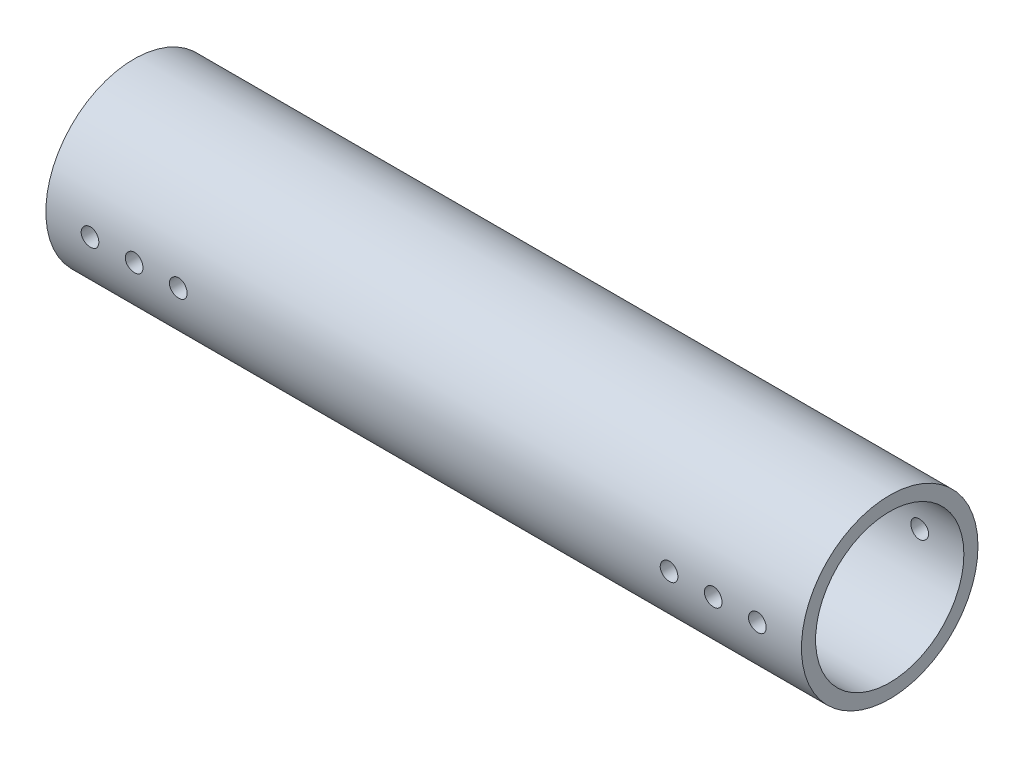
SolidWorks part; units mm, degrees
material "Zoltek Panex 33"
ref_plane "Спереди" through (0, 0, 0) normal (0, 0, 1) x (1, 0, 0)
ref_plane "Сверху" through (0, 0, 0) normal (0, 1, 0) x (1, 0, 0)
ref_plane "Справа" through (0, 0, 0) normal (1, 0, 0) x (0, 0, -1)
other "Configuration Table"
sketch "Эскиз2" plane through (0, 0, 0) normal (1, 0, 0) x (0, 0, -1)
  circle A0 centre (0, 0) radius 25
  circle A1 centre (0, 0) radius 21
  dimension "D1" = 50
  dimension "D2" = 42
extrude "Бобышка-Вытянуть2" add sketch "Эскиз2" along normal blind 214
ref_plane "Плоскость1" through (0, 0, 25) normal (0, 0, 1) x (1, 0, 0)
sketch "Эскиз4" plane through (0, 0, 25) normal (0, 0, 1) x (1, 0, 0)
  line L0 (0, -25) -> (214, -25) construction
  line L1 (214, -25) -> (214, 25) construction
  circle A0 centre (12.5, 0) radius 2.5
  circle A1 centre (201.5, 0) radius 2.5
  circle A2 centre (25, 0) radius 2.5
  circle A3 centre (37.5, 0) radius 2.5
  circle A4 centre (189, 0) radius 2.5
  circle A5 centre (176.5, 0) radius 2.5
  dimension "D1" = 5
  dimension "D4" = 5
  dimension "D6" = 5
  dimension "D8" = 5
  dimension "D10" = 5
  dimension "D11" = 5
  dimension "D2" = 12.5
  dimension "D3" = 25
  dimension "D5" = 12.5
  dimension "D7" = 12.5
  dimension "D9" = 12.5
  dimension "15" = 12.5
  dimension "D12" = 12.5
extrude "Вырез-Вытянуть2" cut sketch "Эскиз4" against normal through all and the other way blind 10 contours A0 | A1 | A2 | A3 | A5 | A4
equation "\"Diameter\"= 50мм"
equation "\"D1@Эскиз2\"= \"Diameter\""
equation "\"Length\"= 214мм"
equation "\"Thickness\"= 4мм"
equation "\"D1@Бобышка-Вытянуть2\"= \"Length\""
equation "\"D2@Эскиз2\" = \"Diameter\" - \"Thickness\" * 2"
equation "\"D4@Эскиз4\"=\"D1@Эскиз4\""
equation "\"D5@Эскиз4\"=\"D2@Эскиз4\""
equation "\"D3@Эскиз4\"=\"Diameter\"/2"
equation "\"D6@Эскиз4\"=\"D1@Эскиз4\""
equation "\"D8@Эскиз4\"=\"D6@Эскиз4\""
equation "\"D10@Эскиз4\"=\"D4@Эскиз4\""
equation "\"D11@Эскиз4\"=\"D4@Эскиз4\""
equation "\"D9@Эскиз4\"=\"D7@Эскиз4\""
